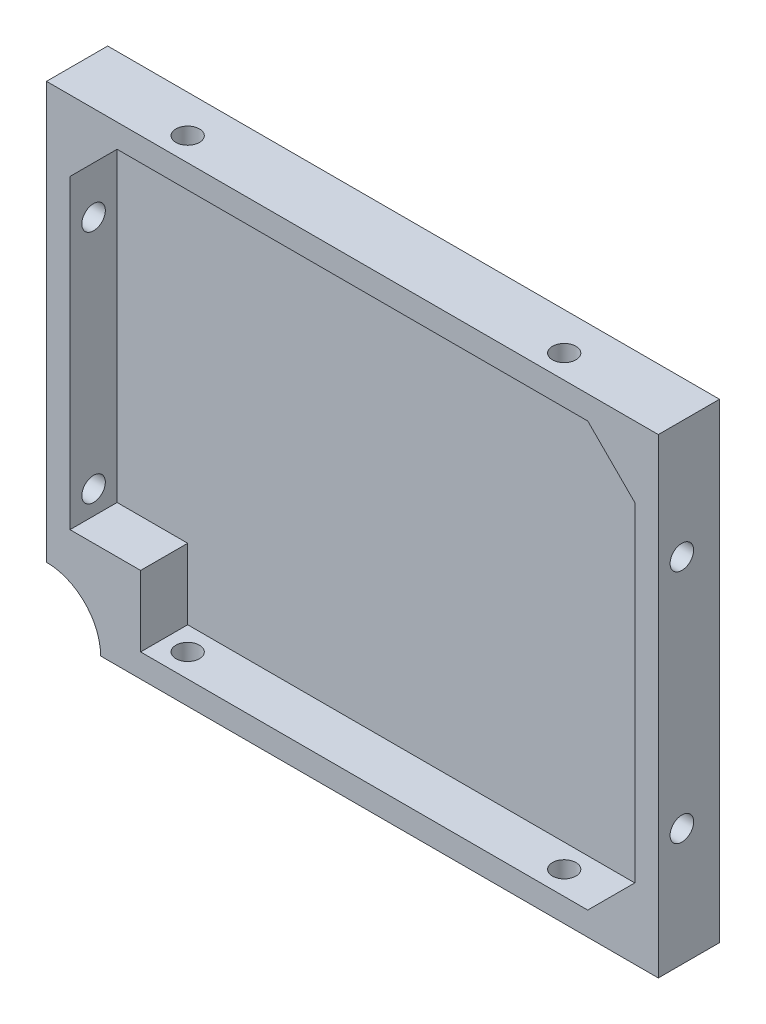
SolidWorks part; units mm, degrees
ref_plane "Plan de face" through (0, 0, 0) normal (0, 0, 1) x (1, 0, 0)
ref_plane "Plan de dessus" through (0, 0, 0) normal (0, 1, 0) x (1, 0, 0)
ref_plane "Plan de droite" through (0, 0, 0) normal (1, 0, 0) x (0, 0, -1)
sketch "Esquisse1" plane through (0, 0, 0) normal (0, 0, 1) x (1, 0, 0)
  line L0 (44.1184, 33.7284) -> (54.1184, 33.7284)
  line L1 (-75.8816, 33.7284) -> (44.1184, 33.7284)
  line L2 (-75.8816, 33.7284) -> (-75.8816, -66.2716)
  line L3 (-75.8816, -66.2716) -> (54.1184, -66.2716)
  line L4 (54.1184, 23.7284) -> (54.1184, -66.2716)
  line L5 (54.1184, 33.7284) -> (54.1184, 23.7284)
  point P6 (54.1184, 33.7284)
  dimension "D1" = 130
  dimension "D2" = 100
extrude "Boss.-Extru.1" add sketch "Esquisse1" along normal blind 13
shell "Coque1" thickness 5 removed face at (-10.8816, -16.2716, 13)
sketch "Esquisse2" plane through (-75.8816, 0, 0) normal (-1, 0, 0) x (0, 0, 1)
  line L0 (13, 33.7284) -> (13, -66.2716) construction
  line L1 (13, 33.7284) -> (0, 33.7284) construction
  line L2 (13, -66.2716) -> (0, -66.2716) construction
  circle A0 centre (8, 8.7284) radius 2.5
  circle A1 centre (8, -41.2716) radius 2.5
  dimension "D1" = 5
  dimension "D2" = 5
  dimension "D3" = 5
  dimension "D4" = 5
  dimension "D5" = 25
  dimension "D6" = 25
extrude "Enlèv. mat.-Extru.1" cut sketch "Esquisse2" against normal up to surface (130 mm away) contours A1 | A0 region at (-75.8816, -41.2716, 8) up to face at (54.1184, -16.2716, 6.5)
sketch "Esquisse3" plane through (0, -66.2716, 0) normal (0, -1, 0) x (1, 0, 0)
  line L0 (-75.8816, 13) -> (54.1184, 13) construction
  line L2 (54.1184, 13) -> (54.1184, 0) construction
  line L3 (-75.8816, 13) -> (-75.8816, 0) construction
  circle A0 centre (-50.8816, 8) radius 2.5
  circle A1 centre (29.1184, 8) radius 2.5
  dimension "D1" = 5
  dimension "D2" = 5
  dimension "D3" = 5
  dimension "D4" = 5
  dimension "D5" = 25
  dimension "D6" = 25
extrude "Enlèv. mat.-Extru.2" cut sketch "Esquisse3" against normal up to surface (100 mm away) up to face at (-10.8816, 33.7284, 6.5)
sketch "Esquisse4" plane through (0, 0, 3) normal (0, 0, 1) x (1, 0, 0)
  line L0 (-60.8816, 28.7284) -> (-70.8816, 18.7284)
  line L1 (49.1184, 28.7284) -> (-70.8816, 28.7284) construction
  line L2 (-70.8816, 28.7284) -> (-70.8816, -61.2716) construction
  line L3 (-70.8816, 18.7284) -> (-70.8816, 28.7284)
  line L4 (-70.8816, 28.7284) -> (-60.8816, 28.7284)
  line L5 (49.1184, 28.7284) -> (49.1184, 18.7284)
  line L6 (49.1184, -61.2716) -> (49.1184, 28.7284) construction
  line L7 (49.1184, 18.7284) -> (39.1184, 28.7284)
  line L8 (39.1184, 28.7284) -> (49.1184, 28.7284)
  line L9 (49.1184, 28.7284) -> (-70.8816, 28.7284) construction
  line L10 (49.1184, -61.2716) -> (49.1184, -51.2716)
  line L11 (49.1184, -51.2716) -> (39.1184, -61.2716)
  line L12 (-70.8816, -61.2716) -> (49.1184, -61.2716) construction
  line L13 (39.1184, -61.2716) -> (49.1184, -61.2716)
  line L14 (-70.8816, -46.2716) -> (-55.8816, -46.2716)
  line L16 (-70.8816, 28.7284) -> (-70.8816, -61.2716) construction
  line L17 (-55.8816, -46.2716) -> (-55.8816, -61.2716)
  line L18 (-55.8816, -61.2716) -> (-70.8816, -61.2716)
  line L19 (-70.8816, -61.2716) -> (-70.8816, -46.2716)
  dimension "D1" = 10
  dimension "D2" = 10
  dimension "D3" = 10
  dimension "D4" = 10
  dimension "D5" = 10
  dimension "D6" = 10
  dimension "D7" = 15
  dimension "D8" = 15
extrude "Boss.-Extru.2" add sketch "Esquisse4" along normal up to surface (10 mm away) up to face at (-10.8816, -16.2716, 13)
sketch "Esquisse6" plane through (0, 0, 13) normal (0, 0, 1) x (1, 0, 0)
  circle A0 centre (-75.8816, -66.2716) radius 11.5
  dimension "D1" = 23
extrude "Enlèv. mat.-Extru.4" cut sketch "Esquisse6" against normal up to surface (13 mm away) up to face at (-10.8816, -16.2716, 0)
